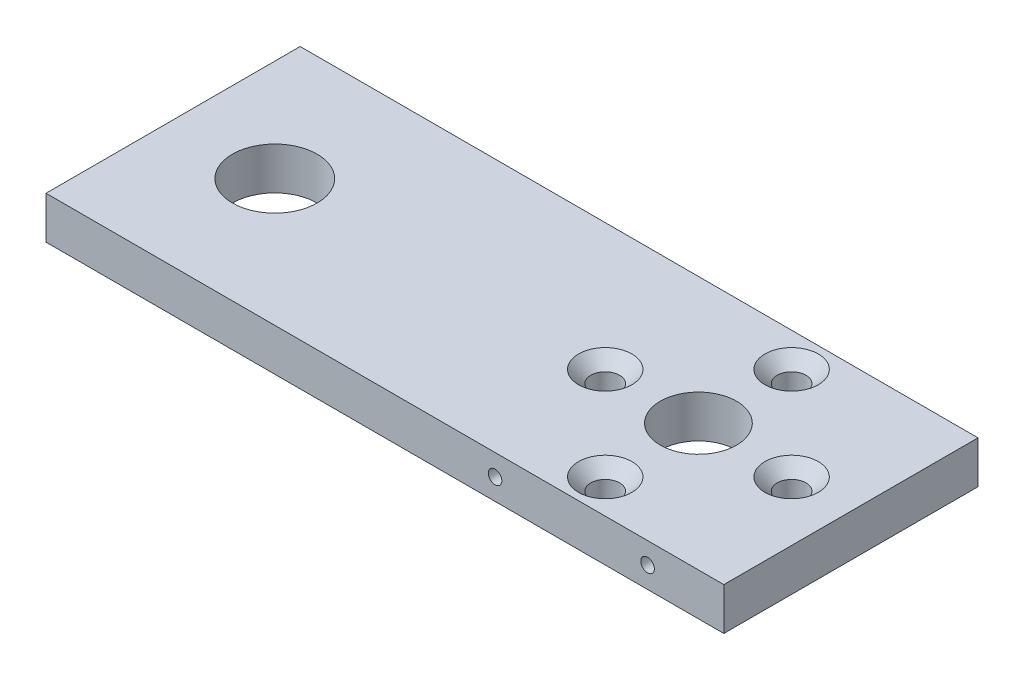
SolidWorks part; units mm, degrees
ref_plane "Front Plane" through (0, 0, 0) normal (0, 0, 1) x (1, 0, 0)
ref_plane "Top Plane" through (0, 0, 0) normal (0, 1, 0) x (1, 0, 0)
ref_plane "Right Plane" through (0, 0, 0) normal (1, 0, 0) x (0, 0, -1)
sketch "Sketch1" plane through (0, 0, 0) normal (0, 1, 0) x (1, 0, 0)
  line L0 (-57.4262, 0) -> (48.7466, 0) construction
  line L3 (-37.0022, 0) -> (-37.0022, 15)
  line L7 (42.9978, -15) -> (42.9978, 15)
  line L10 (-37.0022, 15) -> (42.9978, 15)
  line L11 (42.9978, -15) -> (-37.0022, -15)
  line L12 (-37.0022, -15) -> (-37.0022, 0)
  circle A2 centre (-25, 0) radius 5
  circle A3 centre (25, 0) radius 4.5
  point P12 (-7.4712, -0.16)
  dimension "D1" = 10
  dimension "D2" = 30
  dimension "D3" = 50
  dimension "D4" = 80
  dimension "D5" = 15
extrude "Boss-Extrude2" add sketch "Sketch1" along normal blind 5
sketch "Sketch2" plane through (0, 5, 0) normal (0, 1, 0) x (1, 0, 0)
  point P0 (-25, 0)
  point P1 (-35, 0)
  dimension "D1" = 10
ref_axis "Axis1" through (-25, 21.767, 0) along (0, -1, 0)
sketch "Sketch5" plane through (0, 5, 0) normal (0, 1, 0) x (1, 0, 0)
  point P0 (14, 0)
  point P1 (25, 0)
  dimension "D1" = 11
hole_wizard "CSK for M3 Countersunk Flat Head Screw2" positions "Sketch6" profile "Sketch7" countersink size "M3" standard "ISO" end condition through all
sketch "Sketch6" plane through (0, 5, 0) normal (0, 1, 0) x (1, 0, 0)
  point P0 (14, 0)
sketch "Sketch7" plane through (14, 5, 0) normal (1, 0, 0) x (0, 0, 1)
  line L0 (0, 0) -> (0, 5)
  line L1 (0, 5) -> (1.7, 5)
  line L2 (1.7, 5) -> (1.7, 1.45)
  line L3 (1.7, 1.45) -> (3.15, 0)
  line L5 (3.15, 0) -> (0, 0)
  line L6 (-1.7, 1.45) -> (-3.15, 0) construction
  line L11 (0, -6.35) -> (0, 107.95) construction
  dimension "Thru Hole Dia." = 3.4
  dimension "Thru Hole Depth" = 5
  dimension "Near C'Sink Dia." = 6.3
  dimension "Near C'Sink Angle" = 90
ref_axis "Axis2" through (25, 23.0753, 0) along (0, -1, 0)
pattern_circular "CirPattern2" count 4 every 90 about axis through (25, 23.0753, 0) along (0, -1, 0) of "CSK for M3 Countersunk Flat Head Screw2"
sketch "Sketch12" plane through (0, 0, 15) normal (0, 0, 1) x (1, 0, 0)
  line L0 (42.9978, 2.5) -> (14.7058, 2.5) construction
  line L1 (42.9978, 5) -> (42.9978, 0) construction
  point P4 (33.9978, 2.5)
  point P5 (15.9978, 2.5)
  dimension "D1" = 9
  dimension "D2" = 18
hole_wizard "M2 Tapped Hole1" positions "Sketch13" profile "Sketch14" tap size "M2" standard "ISO"
sketch "Sketch13" plane through (0, 0, 15) normal (0, 0, 1) x (1, 0, 0)
  point P0 (15.9978, 2.5)
  point P3 (33.9978, 2.5)
sketch "Sketch14" plane through (15.9978, 2.5, 15) normal (1, 0, 0) x (0, -1, 0)
  line L0 (0, 0) -> (0, 5.4807)
  line L1 (0, 5.4807) -> (0.8, 5)
  line L2 (0.8, 5) -> (0.8, 0)
  line L5 (0.8, 0) -> (0, 0)
  line L10 (0, 5.4807) -> (-0.8, 5) construction
  line L11 (0, -6.35) -> (0, 107.95) construction
  dimension "Tap Drill Dia." = 1.6
  dimension "Tap Drill Depth" = 5
  dimension "Drill Angle" = 118
sketch "Sketch15" plane through (0, 0, -15) normal (0, 0, -1) x (-1, 0, 0)
  point P0 (-33.9978, 2.5)
  point P1 (-15.9978, 2.5)
hole_wizard "M2 Tapped Hole2" positions "Sketch16" profile "Sketch17" tap size "M2" standard "ISO"
sketch "Sketch16" plane through (0, 0, -15) normal (0, 0, -1) x (-1, 0, 0)
  point P0 (-33.9978, 2.5)
  point P3 (-15.9978, 2.5)
sketch "Sketch17" plane through (33.9978, 2.5, -15) normal (1, 0, 0) x (0, 1, 0)
  line L0 (0, 0) -> (0, 5.4807)
  line L1 (0, 5.4807) -> (0.8, 5)
  line L2 (0.8, 5) -> (0.8, 0)
  line L5 (0.8, 0) -> (0, 0)
  line L10 (0, 5.4807) -> (-0.8, 5) construction
  line L11 (0, -6.35) -> (0, 107.95) construction
  dimension "Tap Drill Dia." = 1.6
  dimension "Tap Drill Depth" = 5
  dimension "Drill Angle" = 118
